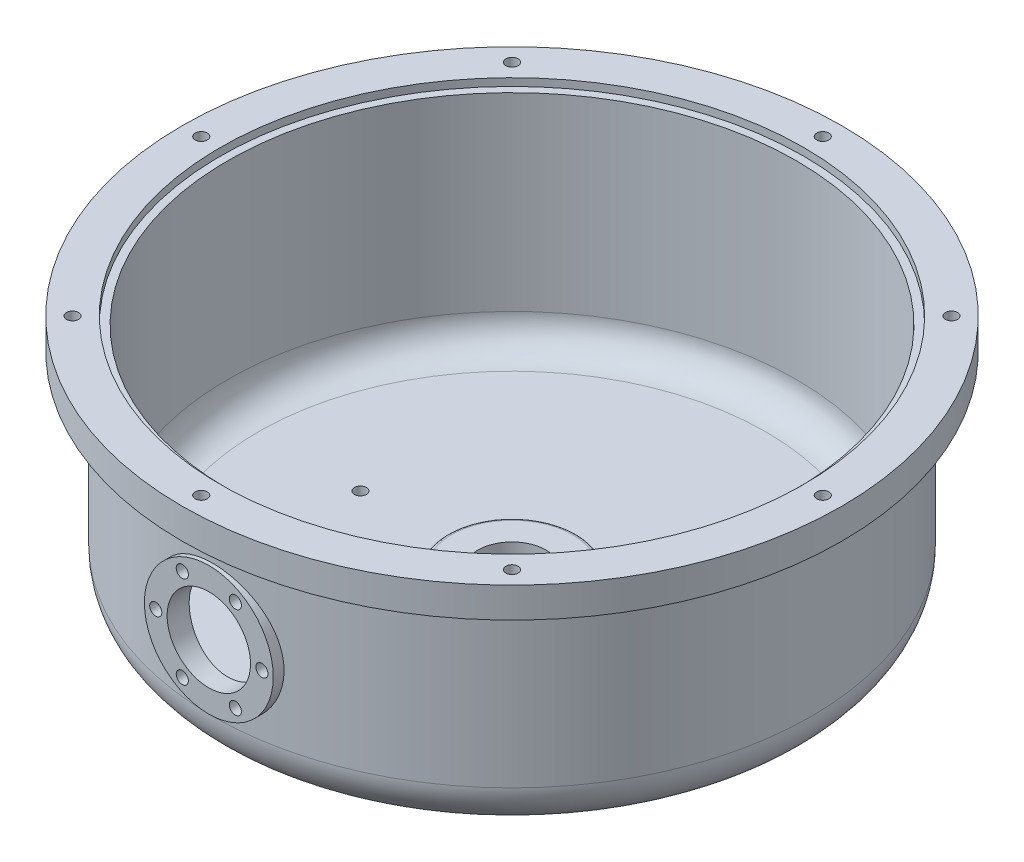
SolidWorks part; units mm, degrees
ref_plane "Front Plane" through (0, 0, 0) normal (0, 0, 1) x (1, 0, 0)
ref_plane "Top Plane" through (0, 0, 0) normal (0, 1, 0) x (1, 0, 0)
ref_plane "Right Plane" through (0, 0, 0) normal (1, 0, 0) x (0, 0, -1)
sketch "Sketch1" plane through (0, 0, 0) normal (0, 0, 1) x (1, 0, 0)
  line L0 (0, 0) -> (0, 320) construction
  line L1 (-435, 320) -> (-385, 320)
  line L2 (-435, 320) -> (-435, 280)
  line L3 (-435, 280) -> (-395, 280)
  line L4 (-395, 280) -> (-395, 0)
  line L6 (-375, 310) -> (-375, 20)
  line L7 (-395, 0) -> (-85, 0)
  line L8 (-375, 20) -> (-85, 20)
  line L10 (-85, 20) -> (-85, 30)
  line L11 (-85, 30) -> (-45, 30)
  line L12 (-45, 30) -> (-45, -5)
  line L13 (-85, 0) -> (-85, -5)
  line L14 (-85, -5) -> (-45, -5)
  line L16 (-375, 310) -> (-385, 310)
  line L17 (-385, 310) -> (-385, 320)
  dimension "D1" = 320
  dimension "D2" = 750
  dimension "D3" = 20
  dimension "D4" = 40
  dimension "D5" = 60
  dimension "D6" = 20
  dimension "D7" = 90
  dimension "D8" = 40
  dimension "D9" = 5
  dimension "D10" = 10
  dimension "D11" = 10
  dimension "D12" = 10
revolve "Revolve1" add sketch "Sketch1" angle 360 about L0
fillet "Fillet1" radius 5 3 edges at (0, 30, -85) (0, 20, -85) (0, 0, -85)
fillet "Fillet2" radius 60 1 edges at (0, 0, -395)
fillet "Fillet3" radius 40 1 edges at (0, 20, -375)
ref_plane "Plane1" through (0, 0, 395) normal (0, 0, 1) x (1, 0, 0)
sketch "Sketch2" plane through (0, 0, 395) normal (0, 0, 1) x (1, 0, 0)
  line L0 (0, 0) -> (0, 320) construction
  line L1 (385, 320) -> (-385, 320) construction
  circle A0 centre (0, 150) radius 55
  circle A1 centre (0, 150) radius 85
  dimension "D1" = 110
  dimension "D3" = 170
  dimension "D2" = 150
extrude "Boss-Extrude1" add sketch "Sketch2" along normal blind 5 and the other way up to surface other way up to face at (0, 60, 395)
sketch "Sketch3" plane through (0, 0, 400) normal (0, 0, 1) x (1, 0, 0)
  circle A0 centre (0, 150) radius 55
extrude "Cut-Extrude1" cut sketch "Sketch3" against normal blind 64
sketch "Sketch4" plane through (0, 0, 400) normal (0, 0, 1) x (1, 0, 0)
  circle A0 centre (0, 150) radius 70 construction
  circle A1 centre (70, 150) radius 8
  circle A2 centre (35, 89.3782) radius 8
  circle A3 centre (-35, 89.3782) radius 8
  circle A4 centre (-70, 150) radius 8
  circle A5 centre (-35, 210.6218) radius 8
  circle A6 centre (35, 210.6218) radius 8
  point P18 (0, 150)
  dimension "D1" = 140
  dimension "D2" = 16
  dimension "D3" = 6
extrude "Cut-Extrude2" cut sketch "Sketch4" against normal blind 15
sketch "Sketch5" plane through (0, 320, 0) normal (0, 1, 0) x (1, 0, 0)
  circle A0 centre (0, 0) radius 410 construction
  circle A1 centre (410, 0) radius 8
  circle A2 centre (289.9138, -289.9138) radius 8
  circle A3 centre (0, -410) radius 8
  circle A4 centre (-289.9138, -289.9138) radius 8
  circle A5 centre (-410, 0) radius 8
  circle A6 centre (-289.9138, 289.9138) radius 8
  circle A7 centre (0, 410) radius 8
  circle A8 centre (289.9138, 289.9138) radius 8
  point P22 (0, 0)
  dimension "D1" = 820
  dimension "D2" = 16
  dimension "D3" = 8
extrude "Cut-Extrude3" cut sketch "Sketch5" against normal through all both
sketch "Sketch6" plane through (0, -5, 0) normal (0, -1, 0) x (1, 0, 0)
  circle A0 centre (0, 0) radius 70 construction
  circle A1 centre (70, 0) radius 8
  circle A2 centre (35, -60.6218) radius 8
  circle A3 centre (-35, -60.6218) radius 8
  circle A4 centre (-70, 0) radius 8
  circle A5 centre (-35, 60.6218) radius 8
  circle A6 centre (35, 60.6218) radius 8
  point P18 (0, 0)
  dimension "D1" = 140
  dimension "D2" = 16
  dimension "D3" = 6
extrude "Cut-Extrude4" cut sketch "Sketch6" against normal blind 20
sketch "Sketch7" plane through (0, 0, 0) normal (0, -1, 0) x (1, 0, 0)
  line L0 (0, 0) -> (-200, 0) construction
  circle A0 centre (-200, 0) radius 8
  dimension "D1" = 16
  dimension "D2" = 200
extrude "Cut-Extrude5" cut sketch "Sketch7" against normal up to surface (20 mm away) up to face at (0, 20, -335)
sketch "Sketch8" plane through (0, 0, 0) normal (0, -1, 0) x (1, 0, 0)
  line L1 (555.8855, -509.259) -> (0, -509.259)
  line L2 (555.8855, -509.259) -> (555.8855, 494.726)
  line L3 (555.8855, 494.726) -> (0, 494.726)
  line L4 (0, -509.259) -> (0, 494.726)
extrude "Cut-Extrude6" [suppressed] cut sketch "Sketch8" against normal through all both and the other way through all
